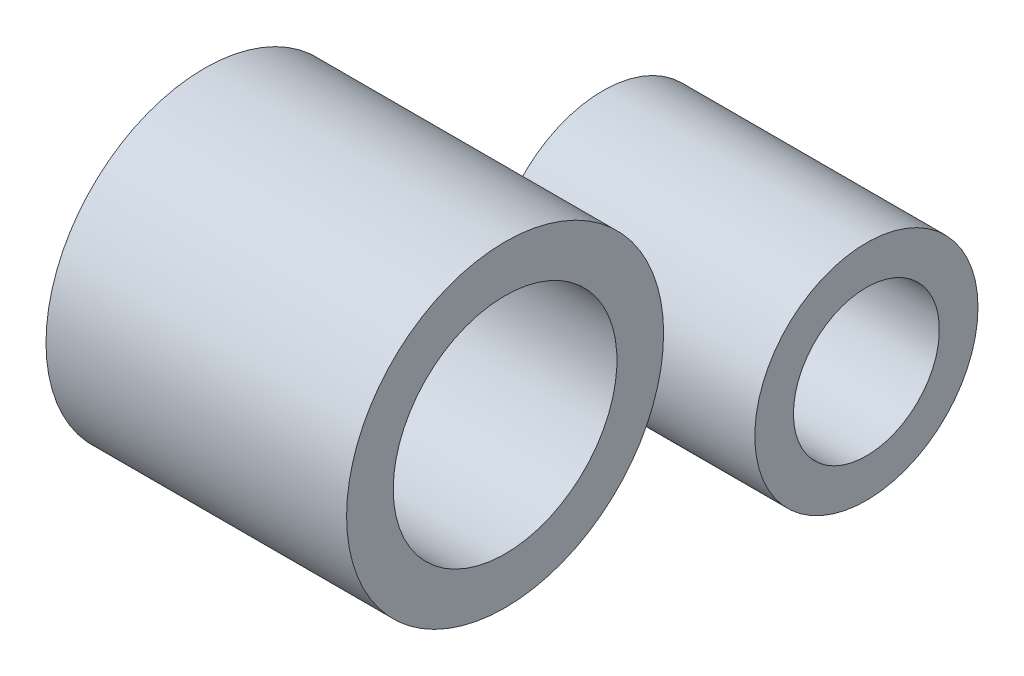
SolidWorks part; units mm, degrees
ref_plane "Front Plane" through (0, 0, 0) normal (0, 0, 1) x (1, 0, 0)
ref_plane "Top Plane" through (0, 0, 0) normal (0, 1, 0) x (1, 0, 0)
ref_plane "Right Plane" through (0, 0, 0) normal (1, 0, 0) x (0, 0, -1)
sketch "Sketch2" plane through (0, 0, 0) normal (1, 0, 0) x (0, 0, -1)
  circle A0 centre (0, 0) radius 27.1025
extrude "Boss-Extrude1" add sketch "Sketch2" along normal blind 64
sketch "Sketch3" plane through (0, 0, 0) normal (1, 0, 0) x (0, 0, -1)
  circle A0 centre (-96.7442, 41.7058) radius 38.4935
extrude "Boss-Extrude2" add sketch "Sketch3" along normal blind 73 separate body
sketch "Sketch7" plane through (0, 0, 0) normal (-1, 0, 0) x (0, 0, 1)
  circle A0 centre (0, 0) radius 17.7221
extrude "Cut-Extrude1" cut sketch "Sketch7" against normal blind 95
sketch "Sketch8" plane through (0, 0, 0) normal (-1, 0, 0) x (0, 0, 1)
  circle A0 centre (96.7442, 41.7058) radius 27.1657
extrude "Cut-Extrude2" cut sketch "Sketch8" against normal blind 95
ref_axis "Axis1" through (0, 0, 0) along (-1, 0, 0)
ref_axis "Axis2" through (0, 41.7058, 96.7442) along (-1, 0, 0)
ref_plane "Plane1" through (0, 26.8108, -3.9653) normal (0, 0.9892, -0.1463) x (1, 0, 0)
ref_plane "Plane2" through (0, 0, 0) normal (0, 0.7102, -0.704) x (1, 0, 0)
sketch "Sketch9" plane through (0, 0, 0) normal (0, 0.7102, -0.704) x (1, 0, 0)
  circle A0 centre (-13.761, -134.9011) radius 57.4217
sketch "Sketch10" plane through (0, 26.8108, -3.9653) normal (0, 0.9892, -0.1463) x (1, 0, 0)
